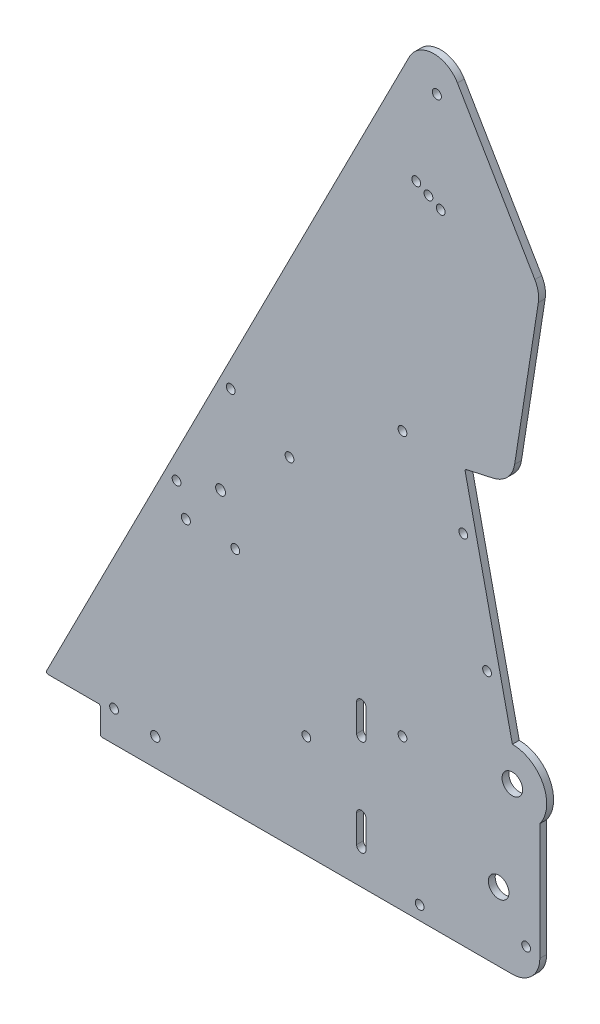
SolidWorks part; units mm, degrees
other "Markup1"
sketch "Sketch5"
ref_plane "Front Plane" through (0, 0, 0) normal (0, 0, 1) x (1, 0, 0)
ref_plane "Top Plane" through (0, 0, 0) normal (0, 1, 0) x (1, 0, 0)
ref_plane "Right Plane" through (0, 0, 0) normal (1, 0, 0) x (0, 0, -1)
sketch "Sketch1" plane through (0, 0, 0) normal (0, 0, 1) x (1, 0, 0)
  line L1 (228.6, -12.7) -> (228.6, 53.975)
  line L2 (178.7547, 351.4131) -> (0, 0)
  line L3 (228.6, 266.7) -> (178.7547, 351.4131)
  line L5 (0, 0) -> (25.4, 0)
  line L6 (25.4, 0) -> (25.4, -12.7)
  line L7 (25.4, -12.7) -> (228.6, -12.7)
  line L9 (215.9, 79.375) -> (193.9097, 178.5667)
  line L10 (193.9097, 178.5667) -> (215.6079, 183.377)
  line L11 (215.6079, 183.377) -> (228.6, 266.7)
  arc A0 (228.6, 53.975) -> (215.9, 79.375) centre (215.9, 63.5) ccw
  dimension "D7" = 12.7
  dimension "D8" = 76.2
  dimension "D10" = 31.75
  dimension "D2" = 279.4
  dimension "D3" = 25.4
  dimension "D4" = 215.9
  dimension "D5" = 394.2644
  dimension "D6" = 203.2
  dimension "D9" = 63.039
  dimension "D11" = 101.6
  dimension "D12" = 12.5
  dimension "D13" = 22.225
extrude "Boss-Extrude1" add sketch "Sketch1" along normal blind 3.175
sketch "Sketch2" plane through (0, 0, 3.175) normal (0, 0, 1) x (1, 0, 0)
  line L0 (178.7547, 351.4131) -> (0, 0) construction
  line L1 (25.4, -12.7) -> (228.6, -12.7) construction
  line L2 (215.9, 79.375) -> (193.9097, 178.5667) construction
  line L3 (193.9097, 178.5667) -> (215.6079, 183.377) construction
  line L4 (215.9, 79.375) -> (193.9097, 178.5667) construction
  line L5 (171.45, 282.575) -> (177.1098, 279.696) construction
  line L6 (178.7547, 351.4131) -> (0, 0) construction
  line L7 (177.1098, 279.696) -> (182.7697, 276.817) construction
  line L10 (228.6, -12.7) -> (228.6, 53.975) construction
  circle A0 centre (64.9432, 94.0578) radius 2.0955
  circle A1 centre (180.975, 322.1643) radius 2.0955
  circle A2 centre (81.0071, 113.733) radius 2.286
  circle A3 centre (193.2078, 152.3944) radius 2.032
  circle A4 centre (215.9, 63.5) radius 4.7625
  circle A7 centre (173.0375, -6.35) radius 2.032
  circle A8 centre (204.203, 102.7985) radius 2.032
  circle A26 centre (209.55, 19.05) radius 4.7625
  circle A28 centre (60.6578, 107.342) radius 2.032
  arc A30 (228.6, 53.975) -> (215.9, 79.375) centre (215.9, 63.5) ccw construction
  circle A31 centre (165.1, 179.3875) radius 2.032
  circle A32 centre (87.825, 93.5227) radius 2.032
  circle A33 centre (112.8724, 142.7633) radius 2.032
  circle A34 centre (85.7052, 156.5826) radius 2.032
  circle A35 centre (171.45, 282.575) radius 2.032
  circle A36 centre (177.1098, 279.696) radius 2.032
  circle A37 centre (182.7697, 276.817) radius 2.032
  dimension "D3" = 4.191
  dimension "D5" = 4.191
  dimension "D9" = 4.572
  dimension "D20" = 9.525
  dimension "D23" = 9.525
  dimension "D18" = 4.064
  dimension "D26" = 4.064
  dimension "D14" = 4.064
  dimension "D10" = 4.064
  dimension "D12" = 4.064
  dimension "D2" = 15.24
  dimension "D6" = 15.24
  dimension "D7" = 25.4
  dimension "D8" = 20.6375
  dimension "D21" = 44.45
  dimension "D22" = 6.35
  dimension "D19" = 160.3375
  dimension "D24" = 44.45
  dimension "D25" = 6.35
  dimension "D27" = 25.4
  dimension "D28" = 50.8
  dimension "D29" = 6.35
  dimension "D17" = 6.35
  dimension "D33" = 55.5625
  dimension "D15" = 114.3
  dimension "D4" = 180.975
  dimension "D11" = 295.275
  dimension "D13" = 171.45
  dimension "D30" = 6.35
  dimension "D16" = 6.35
extrude "Cut-Extrude1" cut sketch "Sketch2" against normal through all
sketch "Sketch7" plane through (0, 0, 3.175) normal (0, 0, 1) x (1, 0, 0)
  line L0 (146.05, 3.175) -> (146.05, 15.875) construction
  line L1 (143.891, 3.175) -> (143.891, 15.875)
  line L2 (148.209, 3.175) -> (148.209, 15.875)
  line L3 (146.05, 47.625) -> (146.05, 60.325) construction
  line L4 (143.891, 47.625) -> (143.891, 60.325)
  line L5 (148.209, 47.625) -> (148.209, 60.325)
  line L6 (25.4, -12.7) -> (228.6, -12.7) construction
  line L12 (228.6, -12.7) -> (228.6, 53.975) construction
  line L13 (25.4, -12.7) -> (228.6, -12.7) construction
  arc A0 (143.891, 3.175) -> (148.209, 3.175) centre (146.05, 3.175) ccw
  arc A1 (148.209, 15.875) -> (143.891, 15.875) centre (146.05, 15.875) ccw
  arc A2 (143.891, 47.625) -> (148.209, 47.625) centre (146.05, 47.625) ccw
  arc A3 (148.209, 60.325) -> (143.891, 60.325) centre (146.05, 60.325) ccw
  circle A8 centre (50.8, 0) radius 2.159
  point P2 (146.05, 9.525)
  point P9 (146.05, 53.975)
  dimension "D1" = 4.318
  dimension "D5" = 4.318
  dimension "D2" = 12.7
  dimension "D3" = 12.7
  dimension "D4" = 44.45
  dimension "D6" = 95.25
  dimension "D7" = 82.55
  dimension "D8" = 15.875
  dimension "D9" = 12.7
extrude "Cut-Extrude2" cut sketch "Sketch7" against normal through all
sketch "Sketch10" plane through (0, 0, 3.175) normal (0, 0, 1) x (1, 0, 0)
  circle A0 centre (120.65, 34.925) radius 2.032
  circle A1 centre (165.1, 57.15) radius 2.032
  dimension "D1" = 4.064
  dimension "D3" = 34.925
  dimension "D2" = 120.65
  dimension "D4" = 63.5
  dimension "D5" = 69.85
extrude "Cut-Extrude3" cut sketch "Sketch10" against normal up to next
fillet "Fillet1" radius 12.7 4 edges at (228.6, -12.7, 1.5875) (178.7547, 351.4131, 1.5875) (215.6079, 183.377, 1.5875) (228.6, 266.7, 1.5875)
fillet "Fillet2" radius 0.7937 4 edges at (25.4, -12.7, 1.5875) (25.4, 0, 1.5875) (193.9097, 178.5667, 1.5875) (0, 0, 1.5875)
sketch "Sketch12" plane through (0, 0, 3.175) normal (0, 0, 1) x (1, 0, 0)
  circle A0 centre (31.75, 1.5875) radius 2.032
  circle A1 centre (173.0375, -6.35) radius 2.032
  circle A2 centre (222.25, 1.5875) radius 2.032
  dimension "D1" = 4.064
extrude "Cut-Extrude5" cut sketch "Sketch12" against normal through all
equation "\"D6@Sketch2\"=\"D2@Sketch2\""
